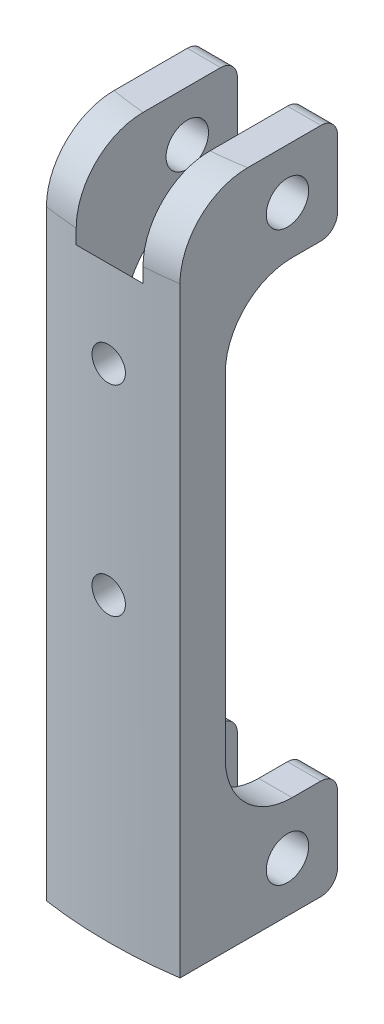
SolidWorks part; units mm, degrees
material "Custom Plastic"
ref_plane "Front Plane" through (0, 0, 0) normal (0, 0, 1) x (1, 0, 0)
ref_plane "Top Plane" through (0, 0, 0) normal (0, 1, 0) x (1, 0, 0)
ref_plane "Right Plane" through (0, 0, 0) normal (1, 0, 0) x (0, 0, -1)
ref_plane "Plane1" through (0, 75, 0) normal (0, 1, 0) x (1, 0, 0)
sketch "Sketch1" plane through (0, 0, 0) normal (0, 1, 0) x (1, 0, 0)
  line L0 (0, 0) -> (0, -67.5) construction
  line L1 (67.5, 0) -> (-67.5, 0) construction
  line L2 (-57.6208, 33.2674) -> (-48.9649, 48.2597)
  line L3 (0, 0) -> (58.4567, 33.75) construction
  line L4 (0, 0) -> (-58.4567, 33.75) construction
  line L5 (-48.9649, 48.2597) -> (-66.2766, 18.2751)
  line L6 (-55.1208, 37.5975) -> (-60.1208, 28.9372)
  line L7 (-60.1208, 28.9372) -> (-41.6363, 18.2652)
  line L8 (0, -66.5347) -> (-17.3116, -66.5347)
  line L9 (-17.3116, -66.5347) -> (17.3116, -66.5347)
  line L10 (-41.6363, 18.2652) -> (-36.6363, 26.9255)
  line L11 (-60.1208, 28.9372) -> (-60.7961, 29.3272)
  line L12 (-55.1208, 37.5975) -> (-36.6363, 26.9255)
  line L13 (-52.6208, 41.9276) -> (-53.906, 42.6697)
  line L14 (-62.6208, 24.6071) -> (-63.906, 25.3492)
  line L15 (-52.6208, 41.9276) -> (-29.8062, 28.7556) construction
  line L16 (-39.8062, 11.4351) -> (-29.8062, 28.7556) construction
  line L17 (-62.6208, 24.6071) -> (-39.8062, 11.4351) construction
  line L18 (57.6208, 33.2674) -> (66.2766, 18.2751)
  line L19 (66.2766, 18.2751) -> (48.9649, 48.2597)
  line L20 (60.1208, 28.9372) -> (55.1208, 37.5975)
  line L21 (55.1208, 37.5975) -> (36.6363, 26.9255)
  line L22 (36.6363, 26.9255) -> (41.6363, 18.2652)
  line L23 (55.1208, 37.5975) -> (55.7961, 37.9874)
  line L24 (60.1208, 28.9372) -> (41.6363, 18.2652)
  line L25 (62.6208, 24.6071) -> (63.906, 25.3492)
  line L26 (-5, -66.5347) -> (5, -66.5347)
  line L27 (5, -66.5347) -> (5, -45.1907)
  line L28 (5, -45.1907) -> (-5, -45.1907)
  line L29 (5, -66.5347) -> (5, -67.3146)
  line L30 (-5, -66.5347) -> (-5, -45.1907)
  line L32 (52.6208, 41.9276) -> (53.906, 42.6697)
  line L33 (62.6208, 24.6071) -> (39.8062, 11.4351) construction
  line L34 (29.8062, 28.7556) -> (39.8062, 11.4351) construction
  line L35 (52.6208, 41.9276) -> (29.8062, 28.7556) construction
  line L36 (-17.3116, -66.5347) -> (-17.3116, -67.3094)
  line L37 (17.3116, -66.5347) -> (17.3116, -67.3094)
  line L38 (-5, -66.5347) -> (-5, -68.5679)
  line L43 (5, -67.3146) -> (5, -68.5679)
  line L44 (-10, -45.1907) -> (10, -45.1907)
  line L45 (-10, -61.5) -> (10, -61.5)
  line L46 (-10, -68.0188) -> (-10, -68.7768)
  line L47 (10, -68.0188) -> (10, -68.7768)
  line L58 (-10, -66.5347) -> (-10, -40.1907)
  line L59 (10, -40.1907) -> (-10, -40.1907)
  line L60 (10, -66.5347) -> (10, -40.1907)
  line L61 (-10, -66.5347) -> (-10, -68.0188)
  line L62 (10, -66.5347) -> (10, -68.0188)
  line L63 (10, -66.5347) -> (10, -67.3146) construction
  circle A0 centre (0, 0) radius 67.5
  circle A1 centre (0, 0) radius 68.75
  circle A2 centre (0, 0) radius 69.5
  circle A4 centre (0, 0) radius 3.975
  circle A5 centre (0, 0) radius 11.1125
  point P14 (0, 0)
  point P26 (-39.1363, 22.5954)
  point P39 (0, -45.1907)
  point P51 (39.1363, 22.5954)
  point P58 (0, 0)
  point P67 (0, 0)
  point P68 (0, 0)
  point P71 (0, 0)
  point P81 (0, 0)
  dimension "D1" = 135
  dimension "D2" = 137.5
  dimension "D3" = 35
  dimension "D5" = 30
  dimension "D11" = 7.95
  dimension "D12" = 22.225
  dimension "D13" = 139
  dimension "D8" = 3
  dimension "D9" = 2
  dimension "D10" = 22.3093
  dimension "D4" = 30
  dimension "D7" = 5
  dimension "D14" = 6
  dimension "D6" = 5
sketch "Sketch16" plane through (0, 75, 0) normal (0, -1, 0) x (1, 0, 0)
  line L0 (-17.3116, 66.5347) -> (17.3116, 66.5347)
  line L1 (-5, 66.5347) -> (-5, 45.1907)
  line L2 (-5, 45.1907) -> (5, 45.1907)
  line L3 (5, 45.1907) -> (5, 67.3146)
  line L4 (0, 67.5) -> (0, 0) construction
  line L5 (-67.5, 0) -> (67.5, 0) construction
  line L14 (0, 0) -> (58.4567, -33.75) construction
  line L15 (0, 0) -> (-58.4567, -33.75) construction
  line L16 (-10, 66.5347) -> (-10, 40.1907) construction
  line L17 (-10, 40.1907) -> (10, 40.1907) construction
  line L18 (10, 40.1907) -> (10, 68.0188) construction
  line L19 (-66.2766, -18.2751) -> (-48.9649, -48.2597)
  line L20 (-48.9649, -48.2597) -> (-55.1208, -37.5975)
  line L21 (-55.1208, -37.5975) -> (-36.6363, -26.9255)
  line L22 (-36.6363, -26.9255) -> (-41.6363, -18.2652)
  line L23 (-41.6363, -18.2652) -> (-60.7961, -29.3272)
  line L25 (5, 45.1907) -> (5, 66.5347) construction
  line L27 (10, 40.1907) -> (10, 66.5347) construction
  line L28 (-63.906, -25.3492) -> (-39.8062, -11.4351) construction
  line L29 (-39.8062, -11.4351) -> (-29.8062, -28.7556) construction
  line L30 (-29.8062, -28.7556) -> (-53.906, -42.6697) construction
  line L31 (48.9649, -48.2597) -> (66.2766, -18.2751)
  line L32 (55.7961, -37.9874) -> (36.6363, -26.9255)
  line L33 (36.6363, -26.9255) -> (41.6363, -18.2652)
  line L34 (41.6363, -18.2652) -> (60.1208, -28.9372)
  line L38 (53.906, -42.6697) -> (29.8062, -28.7556) construction
  line L39 (29.8062, -28.7556) -> (39.8062, -11.4351) construction
  line L40 (39.8062, -11.4351) -> (63.906, -25.3492) construction
  circle A2 centre (0, 0) radius 68.75
  circle A3 centre (0, 0) radius 67.5
  dimension "D1" = 137.5
  dimension "D2" = 135
  dimension "D3" = 5
extrude "Boss-Extrude10" add sketch "Sketch1" along normal blind 100 contours L61 A0 L38 L9 | L61 A1 L38 A0 | L43 A1 L62 A0 | L29 A0 L62 L9 | L38 A0 L29 L9 L8 | L38 A1 L43 A0 | L9 L60 L45 L27 | L58 L9 L30 L45 | L45 L30 L8 L9 L27 | L58 L45 L30 L44 | L45 L60 L44 L27 | L46 A2 L47 A1 region at (-7.5, 0, 64.0174) region at (-7.0616, 0, 66.8252) region at (-7.5034, 0, 67.6949) region at (0, 0, 68.8824) region at (0, 0, 64.0174) region at (0, 0, 66.9882) region at (-7.5, 0, 53.3454) region at (0, 0, 68.0637) region at (7.5034, 0, 67.6949) region at (7.0616, 0, 66.8252) region at (7.5, 0, 64.0174) region at (7.5, 0, 53.3454)
sketch "Sketch17" plane through (10, 0, 0) normal (1, 0, 0) x (0, 0, -1)
  line L0 (-45.1907, 0) -> (-45.1907, 15)
  line L1 (-45.1907, 0) -> (-69.5, 0)
  line L2 (-45.1907, 0) -> (-45.1907, 100)
  line L3 (-45.1907, 100) -> (-69.5, 100)
  line L4 (-69.5, 0) -> (-69.5, 100)
  line L5 (-45.1907, 15) -> (-62, 15)
  line L6 (-62, 15) -> (-62, 85)
  line L7 (-62, 85) -> (-45.1907, 85)
  line L8 (-45.1907, 85) -> (-45.1907, 100)
  line L9 (-45.1907, 100) -> (-52.6907, 100)
  line L10 (-52.6907, 100) -> (-52.6907, 0) construction
  line L11 (-45.1907, 100) -> (-45.1907, 85)
  line L12 (-45.1907, 85) -> (-45.1907, 100)
  line L13 (-45.1907, 92.5) -> (-60.1907, 92.5) construction
  line L14 (-45.1907, 7.5) -> (-55.7103, 7.5) construction
  circle A0 centre (-52.6907, 7.5) radius 3.175
  circle A1 centre (-52.6907, 92.5) radius 3.175
  line M9 (-45.1907, 0) -> (-45.1907, 100)
  dimension "D5" = 6.35
  dimension "D1" = 15
  dimension "D2" = 15
  dimension "D3" = 7.5
  dimension "D4" = 7.5
extrude "Cut-Extrude1" cut sketch "Sketch17" against normal blind 25 contours L7 L6 L5 M9 region at (10, 50, 53.5954)
fillet "Fillet1" radius 10 2 edges at (0, 15, 62) (0, 85, 62)
fillet "Fillet2" radius 2.5 8 edges at (-7.5, 0, 45.1907) (7.5, 0, 45.1907) (-7.5, 15, 45.1907) (7.5, 15, 45.1907) (7.5, 100, 45.1907) (-7.5, 100, 45.1907) (-7.5, 85, 45.1907) (7.5, 85, 45.1907)
fillet "Fillet3" radius 10 1 edges at (0, 100, 69.5)
extrude "Cut-Extrude2" cut sketch "Sketch17<3>" against normal blind 25 contours A1 | A0 region at (10, 7.5, 52.6907) region at (10, 92.5, 52.6907)
sketch "Sketch17<3>" plane through (10, 0, 0) normal (1, 0, 0) x (0, 0, -1) same geometry as "Sketch17"
ref_plane "Plane2" through (0, 0, 68.7768) normal (0, 0, 1) x (1, 0, 0)
sketch "Sketch18" plane through (0, 0, 68.7768) normal (0, 0, 1) x (1, 0, 0)
  line L0 (-5, 99.5541) -> (5, 99.5541)
  line L1 (-10, 100) -> (-5, 100)
  line L2 (-10, 100) -> (-10, 90)
  line L3 (-10, 90) -> (10, 90)
  line L4 (10, 100) -> (10, 90)
  line L5 (-10, 100) -> (-5, 100)
  line L6 (-10, 100) -> (-10, 99.5541)
  line L7 (-10, 99.5541) -> (-5, 99.5541)
  line L8 (-5, 100) -> (-5, 99.5541)
  line L9 (5, 99.5541) -> (10, 100)
  line L10 (5, 99.5541) -> (5, 90)
  line L11 (5, 90) -> (-5, 90)
  line L12 (-5, 90) -> (-5, 99.5541)
  line L13 (-5, 90) -> (-5, 77.5812)
  line L14 (-5, 77.5812) -> (5, 77.5812)
  line L15 (5, 77.5812) -> (5, 90)
  line L16 (5, 100) -> (10, 100)
  line L17 (-5, 100) -> (5, 100)
  line L18 (5, 100) -> (5, 99.5541)
extrude "Cut-Extrude3" cut sketch "Sketch18" against normal mid plane 20 contours L12 L3 L10 L0 | L15 L14 L13 L1 | L18 L17 L8 L0 region at (0, 99.777, 68.7768) region at (0, 94.777, 68.7768)
chamfer "Chamfer1" distance 10 angle 45 1 edges at (0, 90, 61.5)
sketch "Sketch20" plane through (0, 0, 68.7768) normal (0, 0, 1) x (1, 0, 0)
  line L1 (-10, 90) -> (10, 90)
  line L2 (-10, 90) -> (-10, 0)
  line L3 (-10, 0) -> (10, 0)
  line L4 (10, 90) -> (10, 0)
  line L6 (0, 0) -> (0, 90)
  line L7 (0, 45) -> (-10, 45)
  line L8 (-10, 45) -> (10, 45)
  line L9 (-10, 75) -> (10, 75)
  line L10 (-10, 15) -> (10, 15)
  circle A0 centre (0, 75) radius 2.5
  circle A2 centre (0, 45) radius 2.5
  dimension "D1" = 5
  dimension "D2" = 45
  dimension "D3" = 30
extrude "Cut-Extrude4" cut sketch "Sketch20" against normal blind 20 and the other way through all contours A0 | A2
